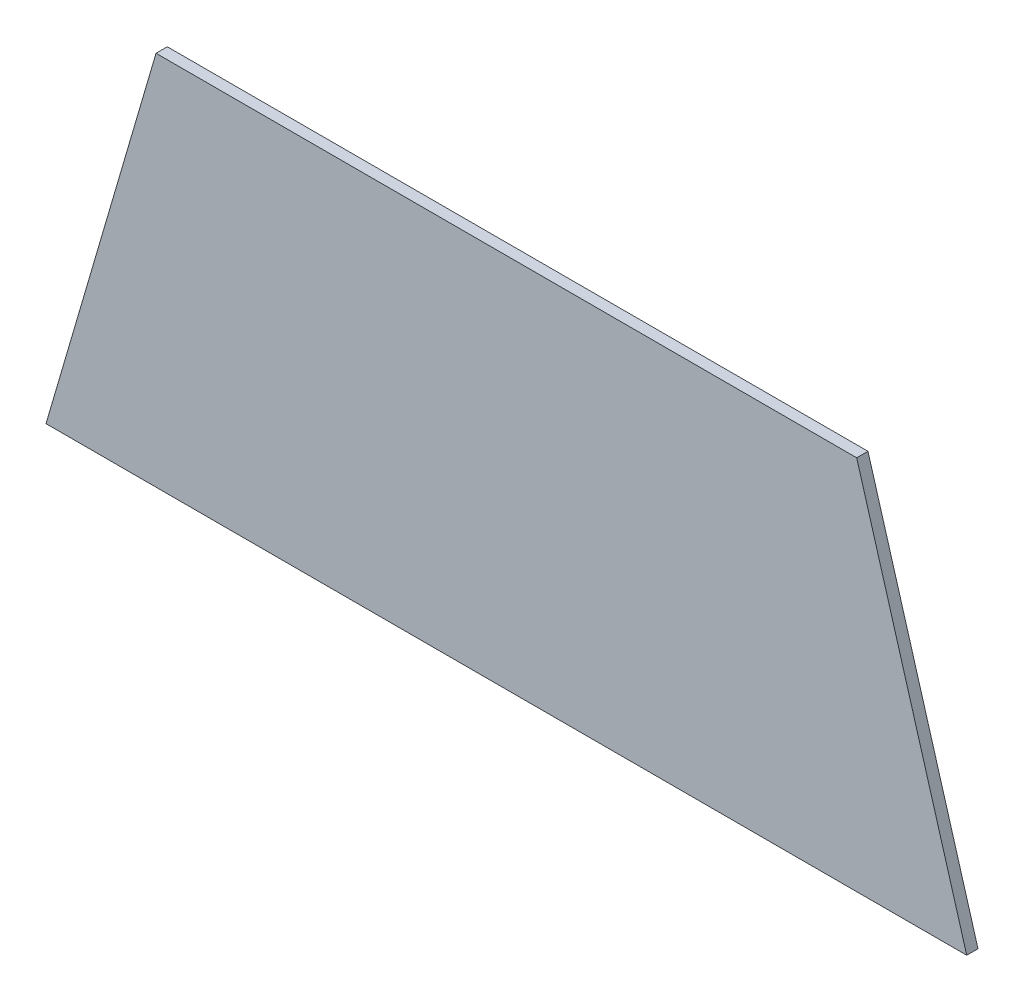
SolidWorks part; units mm, degrees
ref_plane "Front Plane" through (0, 0, 0) normal (0, 0, 1) x (1, 0, 0)
ref_plane "Top Plane" through (0, 0, 0) normal (0, 1, 0) x (1, 0, 0)
ref_plane "Right Plane" through (0, 0, 0) normal (1, 0, 0) x (0, 0, -1)
sketch "Sketch1" plane through (0, 0, 0) normal (0, 0, 1) x (1, 0, 0)
  line L0 (0, 0) -> (245, 0)
  line L3 (122.5, 0) -> (122.5, 100) construction
  line L5 (0, 0) -> (29.2799, 100)
  line L6 (245, 0) -> (215.7201, 100)
  line L7 (29.2799, 100) -> (215.7201, 100)
extrude "Boss-Extrude1" add sketch "Sketch1" along normal blind 3
